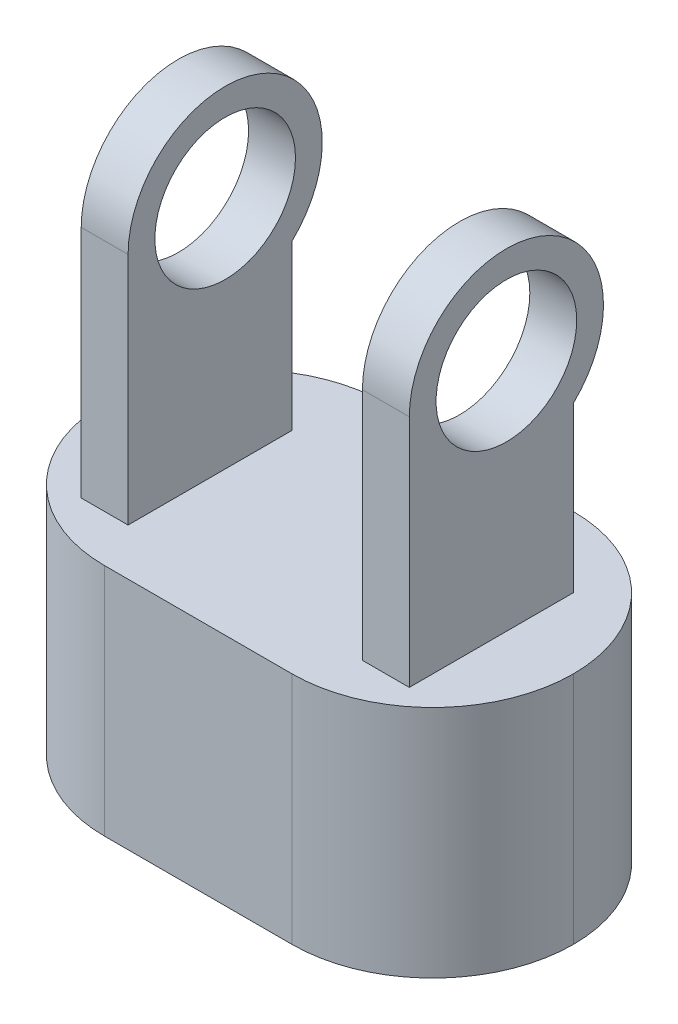
SolidWorks part; units mm, degrees
material "1023 Carbon Steel Sheet (SS)"
ref_plane "Ön Düzlem" through (0, 0, 0) normal (0, 0, 1) x (1, 0, 0)
ref_plane "Üst Düzlem" through (0, 0, 0) normal (0, 1, 0) x (1, 0, 0)
ref_plane "Sağ Düzlem" through (0, 0, 0) normal (1, 0, 0) x (0, 0, -1)
sketch "Sketch1" plane through (0, 0, 0) normal (0, 1, 0) x (1, 0, 0)
  line L0 (-10, 0) -> (10, 0)
  line L1 (10, 0) -> (10, 12)
  line L2 (10, 12) -> (-10, 12)
  line L3 (-10, 12) -> (-10, 0)
  dimension "D1" = 20
  dimension "D2" = 12
extrude "Boss-Extrude1" add sketch "Sketch1" along normal blind 10
sketch "Sketch3" plane through (0, 10, 0) normal (0, 1, 0) x (1, 0, 0)
  line L0 (-6, 0) -> (-6, 12) construction
  line L1 (-10, 0) -> (10, 0) construction
  line L2 (10, 12) -> (-10, 12) construction
  line L3 (6, 0) -> (6, 12) construction
  dimension "D1" = 6
  dimension "D2" = 6
ref_plane "Plane1" through (-6, 0, 0) normal (1, 0, 0) x (0, 0, -1)
sketch "Sketch4" plane through (-6, 0, 0) normal (1, 0, 0) x (0, 0, -1)
  line L0 (2, 10) -> (2, 20)
  line L1 (0, 10) -> (12, 10) construction
  line L3 (9, 17) -> (9, 10)
  line L4 (9, 10) -> (2, 10)
  arc A0 (2, 20) -> (9, 17) centre (6.1429, 20) cw
  circle A1 centre (6.1429, 20) radius 3
  dimension "D5" = 6
  dimension "D1" = 7
  dimension "D2" = 10
  dimension "D3" = 2
extrude "Boss-Extrude2" add sketch "Sketch4" against normal mid plane 2 contours A1 | L0 A0 L3 L4 region at (-6, 20, -6.1429)
mirror "Mirror1" about plane through (0, 0, 0) normal (1, 0, 0) of "Boss-Extrude2"
fillet "Fillet1" radius 6 4 edges at (-10, 5, -12) (10, 5, -12) (10, 5, 0) (-10, 5, 0)
